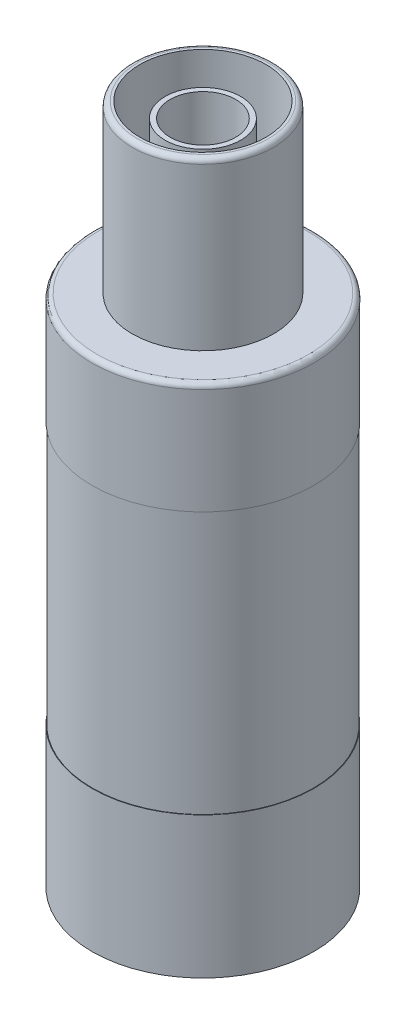
SolidWorks part; units mm, degrees
ref_plane "Спереди" through (0, 0, 0) normal (0, 0, 1) x (1, 0, 0)
ref_plane "Сверху" through (0, 0, 0) normal (0, 1, 0) x (1, 0, 0)
ref_plane "Справа" through (0, 0, 0) normal (1, 0, 0) x (0, 0, -1)
sketch "Эскиз1" plane through (0, 0, 0) normal (0, 1, 0) x (1, 0, 0)
  circle A0 centre (0, 0) radius 11
  dimension "D1" = 22
extrude "Бобышка-Вытянуть1" add sketch "Эскиз1" along normal blind 14
sketch "Эскиз3" plane through (0, 14, 0) normal (0, 1, 0) x (1, 0, 0)
  circle A0 centre (0, 0) radius 10.9
  circle A1 centre (0, 0) radius 11
  circle A2 centre (0, 0) radius 11
  circle A3 centre (0, 0) radius 10.95
  dimension "D1" = 0
  dimension "D2" = 0.1
  dimension "D3" = 0.05
extrude "Бобышка-Вытянуть6" add sketch "Эскиз3" along normal blind 26 contours A3 A0 region at (-10.919, 14, 0)
sketch "Эскиз5" plane through (0, 40, 0) normal (0, 1, 0) x (1, 0, 0)
  circle A0 centre (0, 0) radius 11
  circle A1 centre (0, 0) radius 10.95
  circle A2 centre (0, 0) radius 10.95
  circle M2 centre (0, 0) radius 10.9
  circle M3 centre (0, 0) radius 10.95
  dimension "D1" = 0
  dimension "D2" = 0.05
extrude "Бобышка-Вытянуть7" add sketch "Эскиз5" along normal blind 11 contours M2 | A0 M3 | M3 M2 region at (-10.9689, 40, 0) region at (-10.919, 40, 0) region at (0, 40, 0)
sketch "Эскиз6" plane through (0, 51, 0) normal (0, 1, 0) x (1, 0, 0)
  circle A0 centre (0, 0) radius 7
  circle A1 centre (0, 0) radius 11
  circle A2 centre (0, 0) radius 11
  circle A3 centre (0, 0) radius 3.75
  circle A4 centre (0, 0) radius 3.25
  circle A5 centre (0, 0) radius 6.25
  dimension "D2" = 14
  dimension "D3" = 7.5
  dimension "D4" = 6.5
  dimension "D5" = 12.5
  dimension "D1" = 0
extrude "Бобышка-Вытянуть8" add sketch "Эскиз6" along normal blind 16.5 contours A0 region at (-6.802, 51, 0)
extrude "Бобышка-Вытянуть9" add sketch "Эскиз6<3>" along normal blind 15 contours A3 A4 region at (-3.6439, 51, 0)
sketch "Эскиз6<3>" plane through (0, 51, 0) normal (0, 1, 0) x (1, 0, 0) same geometry as "Эскиз6"
fillet "Скругление1" radius 0.5 1 edges at (0, 51, 11)
fillet "Скругление2" radius 0.5 1 edges at (0, 67.5, 7)
sketch "Эскиз8" plane through (0, 14, 0) normal (0, 1, 0) x (1, 0, 0)
  circle A0 centre (0, 0) radius 9
  circle A1 centre (0, 0) radius 10.9
  circle A2 centre (0, 0) radius 10.9
  dimension "D1" = 0
extrude "Бобышка-Вытянуть10" add sketch "Эскиз8" along normal blind 15 contours A0 region at (0, 14, 0)
sketch "Эскиз9" plane through (0, 29, 0) normal (0, 1, 0) x (1, 0, 0)
  circle A0 centre (0, 0) radius 4.7628
  circle A1 centre (0, 0) radius 9
  circle A2 centre (0, 0) radius 9
  dimension "D1" = 0
extrude "Бобышка-Вытянуть11" add sketch "Эскиз9" along normal blind 15 contours A0 region at (0, 29, 0)
chamfer "Фаска1" distance 4 angle 35 1 edges at (0, 29, 4.7628) first distance on face at (0, 29, 4.7628)
